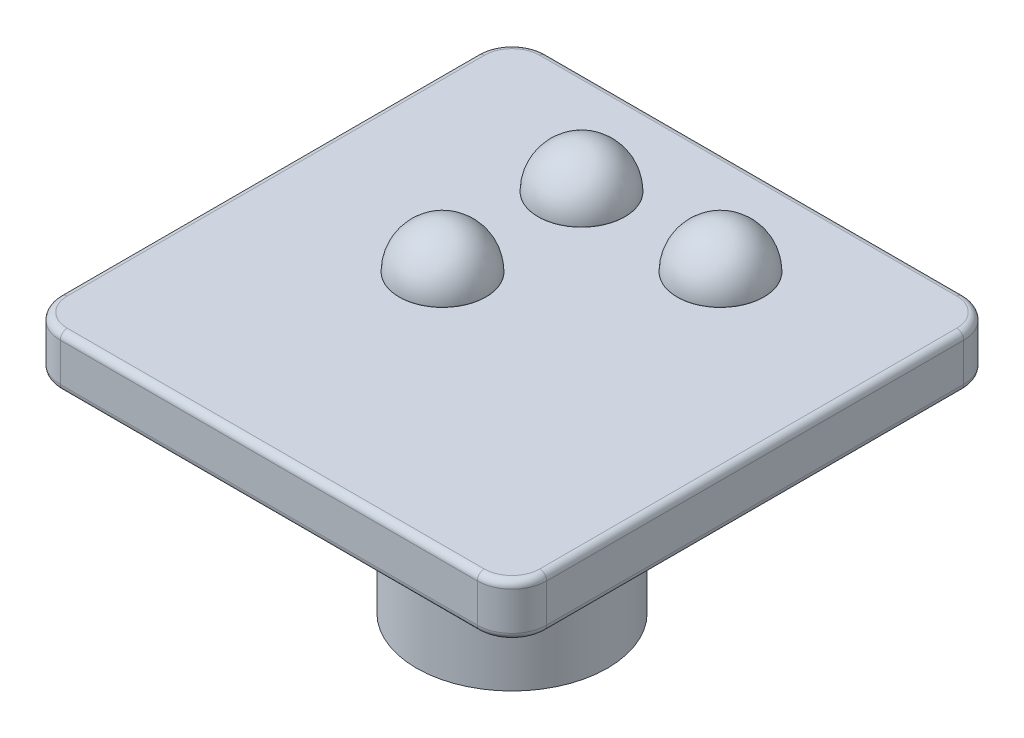
SolidWorks part; units mm, degrees
ref_plane "Front Plane" through (0, 0, 0) normal (0, 0, 1) x (1, 0, 0)
ref_plane "Top Plane" through (0, 0, 0) normal (0, 1, 0) x (1, 0, 0)
ref_plane "Right Plane" through (0, 0, 0) normal (1, 0, 0) x (0, 0, -1)
sketch "Sketch1" plane through (0, 0, 0) normal (0, 1, 0) x (1, 0, 0)
  line L1 (-7.3247, 4.3967) -> (4.6753, 4.3967)
  line L2 (-8.3247, 3.3967) -> (-8.3247, -8.6033)
  line L3 (-7.3247, -9.6033) -> (4.6753, -9.6033)
  line L4 (5.6753, 3.3967) -> (5.6753, -8.6033)
  arc A0 (-8.3247, -8.6033) -> (-7.3247, -9.6033) centre (-7.3247, -8.6033) ccw
  arc A1 (4.6753, -9.6033) -> (5.6753, -8.6033) centre (4.6753, -8.6033) ccw
  arc A2 (4.6753, 4.3967) -> (5.6753, 3.3967) centre (4.6753, 3.3967) cw
  arc A3 (-7.3247, 4.3967) -> (-8.3247, 3.3967) centre (-7.3247, 3.3967) ccw
  point P8 (5.6753, -9.6033)
  point P11 (5.6753, 4.3967)
  point P14 (-8.3247, 4.3967)
  dimension "D3" = 1
  dimension "D1" = 14
  dimension "D2" = 14
extrude "Boss-Extrude1" add sketch "Sketch1" along normal blind 1.5
sketch "Sketch2" plane through (0, 0, 0) normal (0, -1, 0) x (1, 0, 0)
  line L0 (-7.3247, 9.6033) -> (4.6753, 9.6033) construction
  line L1 (5.6753, 8.6033) -> (5.6753, -3.3967) construction
  line L2 (-1.3247, -4.3967) -> (-1.3247, 9.6033) construction
  line L3 (-8.3247, 2.6033) -> (5.6753, 2.6033) construction
  line L4 (-8.3247, -3.3967) -> (-8.3247, 8.6033) construction
  circle A0 centre (-1.3247, 2.6033) radius 2.75
  dimension "D1" = 7
  dimension "D2" = 7
extrude "Boss-Extrude2" add sketch "Sketch2" along normal blind 6
sketch "Sketch3" plane through (0, -6, 0) normal (0, -1, 0) x (1, 0, 0)
  line L0 (-1.3247, 5.3533) -> (-1.3247, -0.1467) construction
  line L1 (-3.3247, 3.1533) -> (0.6753, 3.1533)
  line L2 (-3.3247, 3.1533) -> (-3.3247, 2.0533)
  line L3 (-3.3247, 2.0533) -> (0.6753, 2.0533)
  line L4 (0.6753, 3.1533) -> (0.6753, 2.0533)
  line L5 (-1.8747, 4.6033) -> (-0.7747, 4.6033)
  line L6 (-1.8747, 4.6033) -> (-1.8747, 0.6033)
  line L7 (-1.8747, 0.6033) -> (-0.7747, 0.6033)
  line L8 (-0.7747, 4.6033) -> (-0.7747, 0.6033)
  line L9 (-4.0747, 2.6033) -> (1.4253, 2.6033) construction
  circle A3 centre (-1.3247, 2.6033) radius 2.75 construction
  circle A4 centre (-1.3247, 2.6033) radius 2.75 construction
  point P17 (-1.3247, 4.6033)
  dimension "D7" = 0.55
  dimension "D1" = 4
  dimension "D2" = 1.1
  dimension "D3" = 1.1
  dimension "D4" = 4
  dimension "D5" = 2
  dimension "D6" = 2
  dimension "D8" = 0.55
extrude "Cut-Extrude1" cut sketch "Sketch3" against normal blind 6 contours L8 L5 L6 L1 | L1 L8 L3 L4 | L8 L1 L6 L3 | L6 L1 L2 L3 | L8 L3 L6 L7 region at (-2.5997, -6, 2.6033) region at (-1.3247, -6, 3.8783) region at (-1.3247, -6, 2.6033) region at (-0.0497, -6, 2.6033) region at (-1.3247, -6, 1.3283)
chamfer "Chamfer1" distance 0.3 angle 45 12 edges at (-1.3247, -6, 0.6033) (-1.8747, -6, 1.3283) (-2.5997, -6, 2.0533) (-3.3247, -6, 2.6033) (-2.5997, -6, 3.1533) (-0.7747, -6, 1.3283) (-0.0497, -6, 2.0533) (0.6753, -6, 2.6033) (-0.0497, -6, 3.1533) (-0.7747, -6, 3.8783) (-1.3247, -6, 4.6033) (-1.8747, -6, 3.8783)
fillet "Fillet1" radius 1 1 edges at (-1.3247, 0, -0.1467)
sketch "Sketch4" plane through (0, 1.5, 0) normal (0, 1, 0) x (1, 0, 0)
  line L0 (-1.3247, 4.3967) -> (-1.3247, -9.6033) construction
  line L1 (4.6753, 4.3967) -> (-7.3247, 4.3967) construction
  line L2 (-7.3247, -9.6033) -> (4.6753, -9.6033) construction
  line L3 (5.6753, -2.6033) -> (-8.3247, -2.6033) construction
  line L4 (-8.3247, 3.3967) -> (-8.3247, -8.6033) construction
  line L5 (5.6753, -8.6033) -> (5.6753, 3.3967) construction
  line L6 (-3.3247, 4.3967) -> (-3.3247, -9.6033) construction
  line L7 (0.6753, 4.3967) -> (0.6753, -9.6033) construction
  line L8 (-8.3247, 1.3967) -> (5.6753, 1.3967) construction
  line L9 (5.6753, -6.6033) -> (-8.3247, -6.6033) construction
  circle A0 centre (-3.3247, 1.3967) radius 1.25
  circle A2 centre (-3.3247, -2.6033) radius 1.25
  circle A5 centre (0.6753, 1.3967) radius 1.25
  dimension "D1" = 4
  dimension "D2" = 4
  dimension "D3" = 2
  dimension "D4" = 2
extrude "Boss-Extrude3" add sketch "Sketch4" along normal blind 0.01
dome "Dome1" faces to dome 1 distance 1.25 reverse direction no elliptical dome no face at (-3.3247, 1.51, -0.1467) parameters "D1"=1.25
dome "Dome2" faces to dome 1 distance 1.25 reverse direction no elliptical dome no face at (0.6753, 1.51, -0.1467) parameters "D1"=1.25
dome "Dome3" faces to dome 1 distance 1.25 reverse direction no elliptical dome no face at (-3.3247, 1.51, 3.8533) parameters "D1"=1.25
fillet "Fillet3" radius 0.2 16 edges at (5.3824, 1.5, -4.1038) (5.6753, 1.5, 2.6033) (5.3824, 1.5, 9.3104) (-1.3247, 1.5, 9.6033) (-8.0318, 1.5, 9.3104) (-8.0318, 1.5, -4.1038) (-8.3247, 1.5, 2.6033) (-1.3247, 1.5, -4.3967) (5.3824, 0, 9.3104) (5.6753, 0, 2.6033) (5.3824, 0, -4.1038) (-1.3247, 0, -4.3967) (-8.0318, 0, -4.1038) (-8.3247, 0, 2.6033) (-8.0318, 0, 9.3104) (-1.3247, 0, 9.6033)
